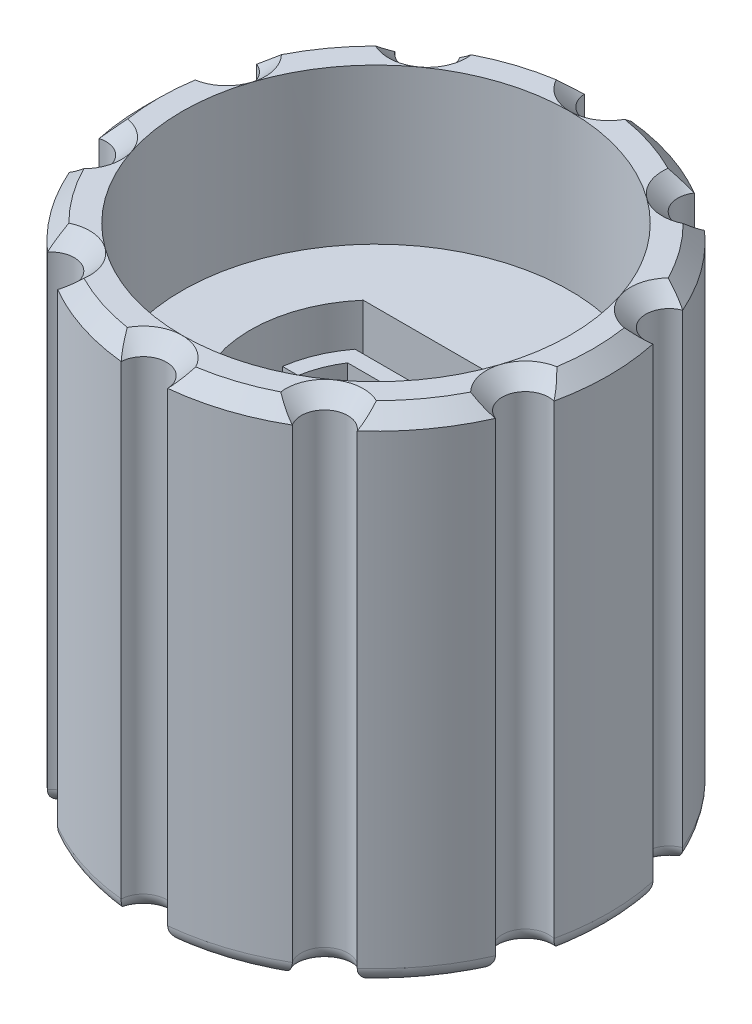
SolidWorks part; units mm, degrees
material "Custom Plastic"
ref_plane "Front Plane" through (0, 0, 0) normal (0, 0, 1) x (1, 0, 0)
ref_plane "Top Plane" through (0, 0, 0) normal (0, 1, 0) x (1, 0, 0)
ref_plane "Right Plane" through (0, 0, 0) normal (1, 0, 0) x (0, 0, -1)
sketch "Sketch1" plane through (0, 0, 0) normal (0, 1, 0) x (1, 0, 0)
  circle A0 centre (0, 0) radius 7.5
  dimension "D1" = 15
extrude "Boss-Extrude1" add sketch "Sketch1" along normal blind 16
sketch "Sketch4" plane through (0, 16, 0) normal (0, 1, 0) x (1, 0, 0)
  line L0 (0, 0) -> (0, -7.5) construction
  line L1 (0, 0) -> (4.4084, -6.0676) construction
  arc A0 (0.7491, -7.4625) -> (-0.7491, -7.4625) centre (0, -7.5) ccw
  circle A1 centre (0, 0) radius 7.5 construction
  circle A2 centre (0, 0) radius 7.5
  arc A3 (-3.7803, -6.4776) -> (-4.9924, -5.597) centre (-4.4084, -6.0676) ccw
  arc A4 (-6.8658, -3.0184) -> (-7.3287, -1.5936) centre (-7.1329, -2.3176) ccw
  arc A5 (-7.3287, 1.5936) -> (-6.8658, 3.0184) centre (-7.1329, 2.3176) ccw
  arc A6 (-4.9924, 5.597) -> (-3.7803, 6.4776) centre (-4.4084, 6.0676) ccw
  arc A7 (-0.7491, 7.4625) -> (0.7491, 7.4625) centre (0, 7.5) ccw
  arc A8 (3.7803, 6.4776) -> (4.9924, 5.597) centre (4.4084, 6.0676) ccw
  arc A9 (6.8658, 3.0184) -> (7.3287, 1.5936) centre (7.1329, 2.3176) ccw
  arc A10 (7.3287, -1.5936) -> (6.8658, -3.0184) centre (7.1329, -2.3176) ccw
  arc A11 (4.9924, -5.597) -> (3.7803, -6.4776) centre (4.4084, -6.0676) ccw
  point P37 (0, 0)
  circle M7 centre (0, 0) radius 7.5
  dimension "D1" = 1.5
  dimension "D3" = 36
  dimension "D2" = 10
extrude "Cut-Extrude3" cut sketch "Sketch4" against normal through all contours A2 A6 | A2 A7 | A2 A8 | A2 A9 | A2 A10 | A2 A11 | A0 M7 | A2 A3 | A2 A4 | A2 A5 region at (0, 16, 7.175) region at (4.2174, 16, 5.8047) region at (-4.2174, 16, 5.8047) region at (6.8239, 16, 2.2172) region at (-6.8239, 16, 2.2172) region at (-6.8239, 16, -2.2172) region at (6.8239, 16, -2.2172) region at (-4.2174, 16, -5.8047) region at (4.2174, 16, -5.8047) region at (0, 16, -7.175)
chamfer "Chamfer1" distance 0.5 angle 45 20 edges at (-3.9676, 16, 5.4609) (-6.0676, 16, 4.4084) (-6.4196, 16, 2.0859) (-7.5, 16, 0) (-6.4196, 16, -2.0859) (-6.0676, 16, -4.4084) (-3.9676, 16, -5.4609) (-2.3176, 16, -7.1329) (0, 16, -6.75) (2.3176, 16, -7.1329) (3.9676, 16, -5.4609) (6.0676, 16, -4.4084) (6.4196, 16, -2.0859) (7.5, 16, 0) (6.4196, 16, 2.0859) (6.0676, 16, 4.4084) (3.9676, 16, 5.4609) (2.3176, 16, 7.1329) (0, 16, 6.75) (-2.3176, 16, 7.1329)
fillet "Fillet1" radius 0.5 20 edges at (-3.9676, 0, 5.4609) (-2.3176, 0, 7.1329) (0, 0, 6.75) (2.3176, 0, 7.1329) (3.9676, 0, 5.4609) (6.0676, 0, 4.4084) (6.4196, 0, 2.0859) (7.5, 0, 0) (6.4196, 0, -2.0859) (6.0676, 0, -4.4084) (3.9676, 0, -5.4609) (2.3176, 0, -7.1329) (0, 0, -6.75) (-2.3176, 0, -7.1329) (-3.9676, 0, -5.4609) (-6.0676, 0, -4.4084) (-6.4196, 0, -2.0859) (-7.5, 0, 0) (-6.4196, 0, 2.0859) (-6.0676, 0, 4.4084)
sketch "Sketch5" plane through (0, 16, 0) normal (0, 1, 0) x (1, 0, 0)
  line L1 (-3.0627, 2.65) -> (3.0627, 2.65)
  arc A1 (-3.0627, 2.65) -> (3.0627, 2.65) centre (0, 0) ccw
  point P8 (0, -4.05)
  dimension "D1" = 8.1
  dimension "D2" = 6.7
extrude "Cut-Extrude4" cut sketch "Sketch5" against normal blind 14
sketch "Sketch6" plane through (0, 2, 0) normal (0, 1, 0) x (1, 0, 0)
  line L0 (2.8249, 2.15) -> (-2.8249, 2.15)
  line L3 (2.5652, 1.65) -> (-2.5652, 1.65)
  line L4 (-3.5146, 0.5) -> (-3.0087, 0.5)
  line L5 (-3.55, 0) -> (-3.05, 0)
  line L6 (-4.05, 0) -> (4.05, 0) construction
  line L8 (3.0087, 0.5) -> (3.5146, 0.5)
  line L9 (-4.05, 0.5) -> (4.05, 0.5) construction
  line L10 (3.05, 0) -> (3.55, 0)
  arc A0 (-2.8249, 2.15) -> (-3.5146, 0.5) centre (0, 0) ccw
  arc A3 (-2.5652, 1.65) -> (-3.0087, 0.5) centre (0, 0) ccw
  arc A6 (3.5146, 0.5) -> (2.8249, 2.15) centre (0, 0) ccw
  arc A7 (-2.8249, 2.15) -> (2.8249, 2.15) centre (0, 0) ccw construction
  arc A8 (3.0087, 0.5) -> (2.5652, 1.65) centre (0, 0) ccw
  arc A9 (-2.5652, 1.65) -> (2.5652, 1.65) centre (0, 0) ccw construction
  arc A10 (-3.05, 0) -> (3.05, 0) centre (0, 0) ccw
  arc A11 (-3.55, 0) -> (3.55, 0) centre (0, 0) ccw
  point P1 (0, 0)
  point P2 (0, -0.5)
  point P3 (0, 0)
  dimension "D1" = 3.55
  dimension "D2" = 3.05
  dimension "D5" = 2.15
  dimension "D6" = 0.5
  dimension "D3" = 0.5
  dimension "D4" = 0.5
extrude "Boss-Extrude2" add sketch "Sketch6" along normal blind 8
sketch "Sketch7" plane through (0, 16, 0) normal (0, 1, 0) x (1, 0, 0)
  line L0 (3.0627, 2.65) -> (-3.0627, 2.65) construction
  line L1 (3.0627, 2.65) -> (-3.0627, 2.65)
  circle A0 centre (0, 0) radius 6.25
  arc A1 (-3.0627, 2.65) -> (3.0627, 2.65) centre (0, 0) ccw construction
  arc A2 (-3.0627, 2.65) -> (3.0627, 2.65) centre (0, 0) ccw
  dimension "D1" = 12.5
extrude "Cut-Extrude5" cut sketch "Sketch7" against normal blind 5
